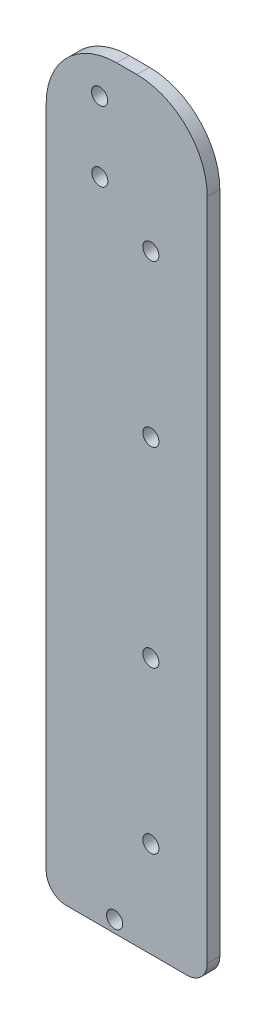
SolidWorks part; units mm, degrees
ref_plane "Front Plane" through (0, 0, 0) normal (0, 0, 1) x (1, 0, 0)
ref_plane "Top Plane" through (0, 0, 0) normal (0, 1, 0) x (1, 0, 0)
ref_plane "Right Plane" through (0, 0, 0) normal (1, 0, 0) x (0, 0, -1)
sketch "Sketch1" plane through (0, 0, 0) normal (0, 0, 1) x (1, 0, 0)
  line L1 (0, -146.6506) -> (0, 146.6506) construction
  line L3 (40.64, 5.08) -> (40.64, 172.72)
  line L5 (35.56, 0) -> (26.416, 0)
  line L7 (66.681, 0) -> (66.681, 88.9) construction
  line L8 (26.416, 0) -> (40.64, 0) construction
  line L9 (26.416, 177.8) -> (26.416, 0) construction
  line L10 (118.1346, 0) -> (-118.1346, 0) construction
  line L11 (66.681, 88.9) -> (0, 88.9) construction
  line L14 (26.416, 0) -> (5.08, 0)
  line L18 (66.681, 88.9) -> (66.681, 177.8) construction
  line L19 (66.681, 177.8) -> (0, 177.8) construction
  line L20 (0, 5.08) -> (0, 172.72)
  line L23 (26.416, 0) -> (20.32, 0) construction
  line L24 (20.32, 0) -> (19.8425, 177.8) construction
  line L25 (20.32, 0) -> (14.732, 0) construction
  line L26 (14.732, 0) -> (14.732, 8.89) construction
  line L27 (14.732, 8.89) -> (14.732, 177.8) construction
  line L28 (26.416, 24.13) -> (0, 24.13) construction
  line L35 (20.32, 0) -> (17.6513, 0) construction
  line L36 (17.6513, 0) -> (17.6513, 177.8) construction
  line L46 (17.78, 190.5) -> (22.86, 190.5)
  line L47 (19.8425, 177.8) -> (19.8425, 190.5) construction
  line L48 (19.8896, 160.274) -> (19.8425, 190.5) construction
  line L49 (19.8425, 190.5) -> (-14.4304, 190.5) construction
  line L50 (19.8896, 160.274) -> (0, 160.274) construction
  circle A0 centre (26.416, 24.13) radius 2.032
  circle A1 centre (26.416, 64.77) radius 2.032
  arc A5 (35.56, 0) -> (40.64, 5.08) centre (35.56, 5.08) ccw
  arc A6 (5.08, 0) -> (0, 5.08) centre (5.08, 5.08) cw
  circle A7 centre (26.416, 113.03) radius 2.032
  circle A8 centre (26.416, 153.67) radius 2.032
  arc A13 (40.64, 172.72) -> (22.86, 190.5) centre (22.86, 172.72) ccw
  arc A14 (0, 172.72) -> (17.78, 190.5) centre (17.78, 172.72) cw
  circle A15 centre (17.272, 3.048) radius 2.032
  circle A17 centre (13.531, 163.449) radius 2.032
  circle A20 centre (13.4925, 181.102) radius 2.032
  point P24 (0, 190.5)
  point P30 (0, 0)
  point P38 (0, 190.5)
  point P42 (0, 185.42)
  point P46 (40.64, 185.0608)
  point P52 (0, 190.5)
  dimension "D7" = 4.064
  dimension "D5" = 24.13
  dimension "D6" = 4.064
  dimension "D9" = 24.13
  dimension "D11" = 88.9
  dimension "D12" = 5.08
  dimension "D13" = 4.064
  dimension "D15" = 4.064
  dimension "D17" = 4.064
  dimension "D19" = 17.78
  dimension "D22" = 4.064
  dimension "D26" = 4.064
  dimension "D20" = 23.368
  dimension "D27" = 6.35
  dimension "D29" = 6.35
  dimension "D1" = 190.5
  dimension "D2" = 40.64
  dimension "D3" = 88.9
  dimension "D4" = 14.224
  dimension "D8" = 40.64
  dimension "D10" = 24.13
  dimension "D14" = 3.048
  dimension "D16" = 40.64
  dimension "D18" = 24.13
  dimension "D21" = 30.226
  dimension "D23" = 20.32
  dimension "D24" = 25.908
  dimension "D28" = 64.77
  dimension "D32" = 2.6687
extrude "Boss-Extrude2" add sketch "Sketch1" along normal blind 3.175
